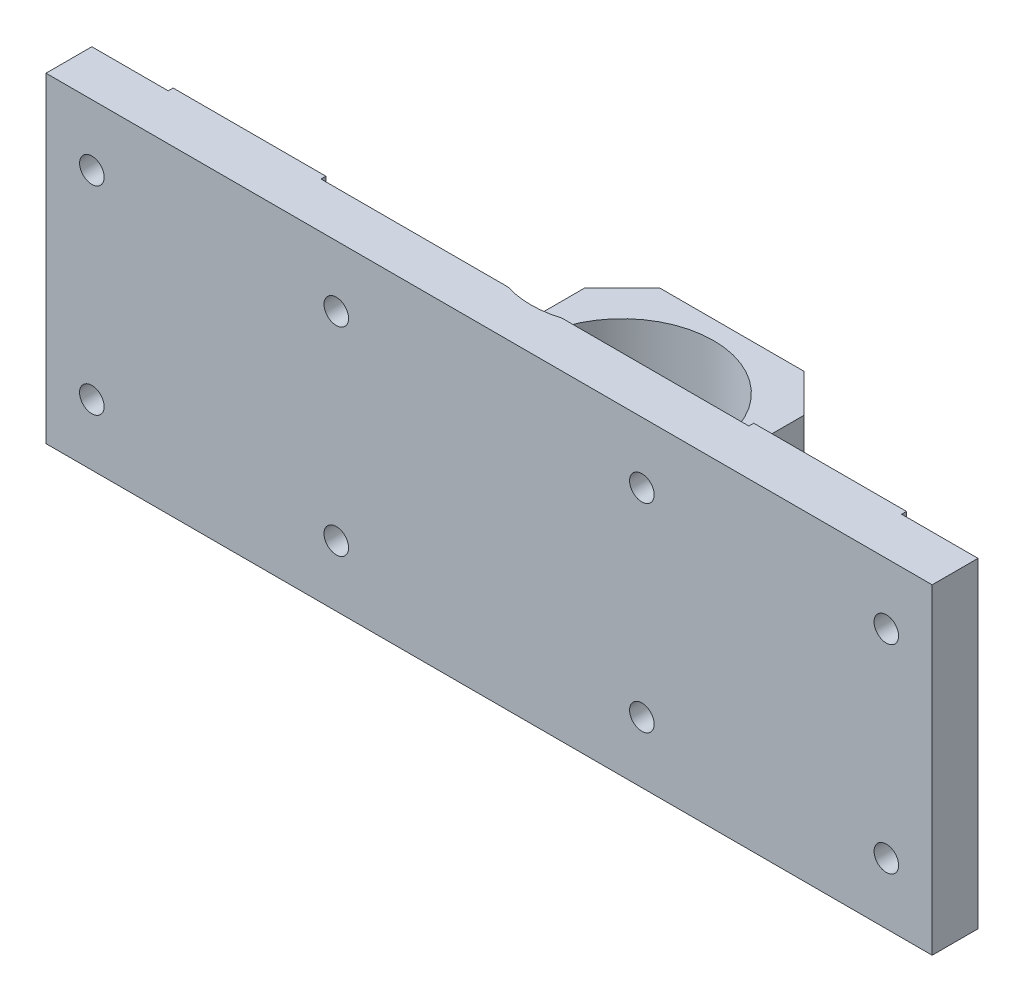
SolidWorks part; units mm, degrees
ref_plane "Front Plane" through (0, 0, 0) normal (0, 0, 1) x (1, 0, 0)
ref_plane "Top Plane" through (0, 0, 0) normal (0, 1, 0) x (1, 0, 0)
ref_plane "Right Plane" through (0, 0, 0) normal (1, 0, 0) x (0, 0, -1)
sketch "Sketch1" plane through (0, 0, 0) normal (0, 0, 1) x (1, 0, 0)
  line L1 (-87.7906, 37.622) -> (96.3594, 37.622)
  line L2 (-87.7906, 37.622) -> (-87.7906, -29.053)
  line L3 (-87.7906, -29.053) -> (96.3594, -29.053)
  line L4 (96.3594, 37.622) -> (96.3594, -29.053)
  dimension "D1" = 184.15
  dimension "D2" = 66.675
extrude "Boss-Extrude1" add sketch "Sketch1" along normal blind 9.525
sketch "Sketch5" plane through (0, 37.622, 0) normal (0, 1, 0) x (1, 0, 0)
  line L0 (10.8884, 0) -> (10.8884, -9.525)
  line L1 (96.3594, 0) -> (-87.7906, 0) construction
  line L2 (96.3594, -9.525) -> (-87.7906, -9.525) construction
  line L3 (-2.3196, 0) -> (-2.3196, -9.525)
  point P8 (4.2844, 0)
  dimension "D1" = 6.604
  dimension "D2" = 6.604
sketch "Sketch6" plane through (0, 37.622, 0) normal (0, 1, 0) x (1, 0, 0)
  arc A0 (10.8884, 0) -> (-2.3196, 0) centre (4.2844, 10.8827) cw
extrude "Cut-Extrude1" cut sketch "Sketch6" against normal through all and the other way through all flip side to cut
sketch "Sketch7" plane through (0, 37.622, 0) normal (0, 1, 0) x (1, 0, 0)
  line L0 (4.2844, -4.7215) -> (4.2844, 18.1385)
  line L1 (-87.7906, -9.525) -> (-87.7906, 0) construction
  circle A1 centre (4.2844, 18.1385) radius 22.8473
  dimension "D1" = 22.86
  dimension "D2" = 92.075
extrude "Boss-Extrude2" add sketch "Sketch7" against normal through all contours A1
sketch "Sketch8" plane through (0, 37.622, 0) normal (0, 1, 0) x (1, 0, 0)
  circle A0 centre (4.2844, 18.1385) radius 18.9865
  dimension "D1" = 37.973
extrude "Cut-Extrude2" cut sketch "Sketch8" against normal blind 61.595
sketch "Sketch9" plane through (0, -23.973, 0) normal (0, 1, 0) x (1, 0, 0)
  circle A0 centre (4.2844, 18.1385) radius 7.9375
  circle A1 centre (4.2844, 18.1385) radius 18.9865 construction
  dimension "D1" = 15.875
  dimension "D2" = 0
extrude "Cut-Extrude3" cut sketch "Sketch9" against normal through all
sketch "Sketch12" plane through (0, 37.622, 0) normal (0, 1, 0) x (1, 0, 0)
  line L0 (27.1317, 18.1385) -> (27.1317, 0)
  line L1 (96.3594, 0) -> (18.1766, 0) construction
  line L2 (27.1317, 0) -> (18.1766, 0)
  line L3 (-18.5629, 18.1385) -> (-18.5629, 0)
  line L4 (-9.6078, 0) -> (-87.7906, 0) construction
  line L5 (-18.5629, 0) -> (-9.6078, 0)
  circle A0 centre (4.2844, 18.1385) radius 22.8473 construction
  arc A1 (18.1766, 0) -> (27.1317, 18.1385) centre (4.2844, 18.1385) ccw
  arc A2 (-9.6078, 0) -> (-18.5629, 18.1385) centre (4.2844, 18.1385) cw
extrude "Boss-Extrude3" add sketch "Sketch12" against normal up to surface (66.675 mm away) up to face at (4.2844, -29.053, -10.201)
sketch "Sketch16" plane through (0, -29.053, 0) normal (0, -1, 0) x (1, 0, 0)
  line L0 (-18.5629, -18.1385) -> (-18.5629, -40.9857)
  line L1 (4.2844, -40.9857) -> (-18.5629, -40.9857)
  arc A0 (-18.5629, -18.1385) -> (27.1317, -18.1385) centre (4.2844, -18.1385) ccw construction
  arc A1 (-18.5629, -18.1385) -> (4.2844, -40.9857) centre (4.2844, -18.1385) ccw
extrude "Boss-Extrude4" add sketch "Sketch16" against normal up to surface (66.675 mm away) up to face at (4.2844, 37.622, -5.0093)
sketch "Sketch18" plane through (0, -29.053, 0) normal (0, -1, 0) x (1, 0, 0)
  line L0 (27.1317, -18.1385) -> (27.1317, -40.9857)
  line L1 (27.1317, -40.9857) -> (4.2844, -40.9857)
  arc A0 (27.1317, -18.1385) -> (4.2844, -40.9857) centre (4.2844, -18.1385) cw
extrude "Boss-Extrude5" add sketch "Sketch18" against normal up to surface (66.675 mm away) up to face at (4.8102, 37.622, -9.5324)
sketch "Sketch19" plane through (0, 37.622, 0) normal (0, 1, 0) x (1, 0, 0)
  line L2 (27.1317, 40.9857) -> (-18.5629, 40.9857) construction
  line L3 (19.2577, 40.9857) -> (27.1317, 40.9857)
  line L6 (-18.5629, 40.9857) -> (-18.5629, 0) construction
  line L8 (-18.5629, 40.9857) -> (-18.5629, 33.1259)
  line L9 (-18.5629, 33.1259) -> (-10.703, 40.9857)
  line L10 (-10.703, 40.9857) -> (-18.5629, 40.9857)
  line L11 (19.2577, 40.9857) -> (27.1317, 33.1117)
  line L12 (27.1317, 0) -> (27.1317, 40.9857) construction
  line L13 (27.1317, 33.1117) -> (27.1317, 40.9857)
  dimension "D1" = 7.8599
  dimension "D2" = 7.874
extrude "Cut-Extrude6" cut sketch "Sketch19" against normal through all
hole_wizard "#10 Clearance Hole1" positions "Sketch23" profile "Sketch24" hole size "#10" standard "ANSI Inch" end condition through all
sketch "Sketch23" plane through (0, 0, 0) normal (0, 0, -1) x (-1, 0, 0)
  line L0 (87.7906, 37.622) -> (87.7906, -29.053) construction
  line L1 (87.7906, -29.053) -> (18.5629, -29.053) construction
  line L2 (18.5629, 37.622) -> (87.7906, 37.622) construction
  line L3 (-96.3594, -29.053) -> (-96.3594, 37.622) construction
  line L4 (-96.3594, 37.622) -> (-27.1317, 37.622) construction
  line L5 (-27.1317, -29.053) -> (-96.3594, -29.053) construction
  point P0 (78.2656, 24.922)
  point P2 (78.2656, -16.353)
  point P4 (-86.8344, -16.353)
  point P6 (-86.8344, 24.922)
  dimension "D1" = 9.525
  dimension "D2" = 12.7
  dimension "D3" = 12.7
  dimension "D4" = 9.525
  dimension "D5" = 9.525
  dimension "D6" = 12.7
  dimension "D7" = 12.7
  dimension "D8" = 9.525
sketch "Sketch24" plane through (-78.2656, 24.922, 0) normal (1, 0, 0) x (0, 1, 0)
  line L0 (0, 0) -> (0, 9.525)
  line L1 (0, 9.525) -> (2.5527, 9.525)
  line L2 (2.5527, 9.525) -> (2.5527, 0)
  line L5 (2.5527, 0) -> (0, 0)
  line L11 (0, -6.35) -> (0, 107.95) construction
  dimension "Thru Hole Dia." = 5.1054
  dimension "Thru Hole Depth" = 9.525
hole_wizard "#10 Clearance Hole2" positions "Sketch25" profile "Sketch26" hole size "#10" standard "ANSI Inch" end condition through all
sketch "Sketch25" plane through (0, 0, 0) normal (0, 0, -1) x (-1, 0, 0)
  line L0 (87.7906, -29.053) -> (18.5629, -29.053) construction
  line L2 (18.5629, 37.622) -> (87.7906, 37.622) construction
  line L3 (-96.3594, 37.622) -> (-27.1317, 37.622) construction
  line L5 (-27.1317, -29.053) -> (-96.3594, -29.053) construction
  circle A0 centre (78.2656, -16.353) radius 2.5527 construction
  circle A1 centre (78.2656, 24.922) radius 2.5527 construction
  circle A2 centre (-86.8344, 24.922) radius 2.5527 construction
  circle A3 centre (-86.8344, -16.353) radius 2.5527 construction
  point P0 (27.4656, -16.353)
  point P2 (27.4656, 24.922)
  point P4 (-36.0344, 24.922)
  point P6 (-36.0344, -16.353)
  dimension "D1" = 12.7
  dimension "D2" = 50.8
  dimension "D3" = 50.8
  dimension "D4" = 12.7
  dimension "D5" = 12.7
  dimension "D6" = 50.8
  dimension "D7" = 50.8
  dimension "D8" = 12.7
sketch "Sketch26" plane through (-27.4656, -16.353, 0) normal (1, 0, 0) x (0, 1, 0)
  line L0 (0, 0) -> (0, 9.525)
  line L1 (0, 9.525) -> (2.5527, 9.525)
  line L2 (2.5527, 9.525) -> (2.5527, 0)
  line L5 (2.5527, 0) -> (0, 0)
  line L11 (0, -6.35) -> (0, 107.95) construction
  dimension "Thru Hole Dia." = 5.1054
  dimension "Thru Hole Depth" = 9.525
sketch "Sketch31" plane through (0, 0, -40.9857) normal (0, 0, -1) x (-1, 0, 0)
  line L1 (-19.2577, -29.053) -> (10.703, -29.053)
  line L2 (-19.2577, -29.053) -> (-19.2577, 37.622)
  line L3 (-19.2577, 37.622) -> (10.703, 37.622)
  line L4 (10.703, -29.053) -> (10.703, 37.622)
extrude "Boss-Extrude6" [suppressed] add sketch "Sketch31" along normal blind 2.54
hole_wizard "3/16 (0.1875) Diameter Hole3" positions "Sketch32" profile "Sketch33" hole size "3/16" standard "ANSI Inch" end condition up to next
sketch "Sketch32" plane through (-25.8444, 0, -25.8444) normal (-0.7071, 0, -0.7071) x (-0.7071, 0, 0.7071)
  line L0 (-10.2976, -29.053) -> (-21.4131, -29.053) construction
  line L1 (-10.2976, -29.053) -> (-10.2976, 37.622) construction
  point P0 (-15.3776, -20.163)
  point P2 (-15.3776, -7.463)
  dimension "D1" = 8.89
  dimension "D2" = 12.7
  dimension "D3" = 5.08
sketch "Sketch33" plane through (-14.9708, -20.163, -36.718) normal (0, 1, 0) x (-0.7071, 0, 0.7071)
  line L0 (0, 0) -> (0, 7.7726)
  line L1 (0, 7.7726) -> (2.3812, 7.7726)
  line L2 (2.3812, 7.7726) -> (2.3812, 0)
  line L5 (2.3812, 0) -> (0, 0)
  line L11 (0, -6.35) -> (0, 107.95) construction
  dimension "Thru Hole Dia." = 4.7625
  dimension "Thru Hole Depth" = 7.7726
hole_wizard "3/16 (0.1875) Diameter Hole4" positions "Sketch34" profile "Sketch35" hole size "3/16" standard "ANSI Inch" end condition up to next
sketch "Sketch34" plane through (30.1217, 0, -30.1217) normal (0.7071, 0, -0.7071) x (-0.7071, 0, -0.7071)
  line L0 (15.3641, -29.053) -> (4.2285, -29.053) construction
  line L1 (4.2285, -29.053) -> (4.2285, 37.622) construction
  point P0 (9.3085, -20.163)
  point P2 (9.3085, -7.463)
  dimension "D1" = 8.89
  dimension "D2" = 12.7
  dimension "D3" = 5.08
sketch "Sketch35" plane through (23.5395, -20.163, -36.7038) normal (0, 1, 0) x (-0.7071, 0, -0.7071)
  line L0 (0, 0) -> (0, 7.7629)
  line L1 (0, 7.7629) -> (2.3812, 7.7629)
  line L2 (2.3812, 7.7629) -> (2.3812, 0)
  line L5 (2.3812, 0) -> (0, 0)
  line L11 (0, -6.35) -> (0, 107.95) construction
  dimension "Thru Hole Dia." = 4.7625
  dimension "Thru Hole Depth" = 7.7629
sketch "Sketch36" plane through (0, 0, 0) normal (0, 0, -1) x (-1, 0, 0)
  line L0 (-96.3594, 37.622) -> (-27.1317, 37.622) construction
  line L1 (-80.4844, 37.622) -> (-48.7344, 37.622)
  line L2 (-80.4844, 37.622) -> (-80.4844, -29.053)
  line L3 (-80.4844, -29.053) -> (-48.7344, -29.053)
  line L4 (-48.7344, 37.622) -> (-48.7344, -29.053)
  line L5 (-27.1317, -29.053) -> (-96.3594, -29.053) construction
  line L6 (18.5629, 37.622) -> (87.7906, 37.622) construction
  line L7 (40.1656, 37.622) -> (71.9156, 37.622)
  line L8 (40.1656, 37.622) -> (40.1656, -29.053)
  line L9 (40.1656, -29.053) -> (71.9156, -29.053)
  line L10 (71.9156, 37.622) -> (71.9156, -29.053)
  line L11 (87.7906, -29.053) -> (18.5629, -29.053) construction
  line L12 (87.7906, 37.622) -> (87.7906, -29.053) construction
  line L13 (-96.3594, -29.053) -> (-96.3594, 37.622) construction
  dimension "D1" = 15.875
  dimension "D2" = 31.75
  dimension "D3" = 15.875
  dimension "D4" = 31.75
extrude "Boss-Extrude7" add sketch "Sketch36" along normal blind 1.016
ref_plane "Plane1" through (4.2844, 0, 0) normal (1, 0, 0) x (0, 0, -1)
sketch "Sketch37" plane through (27.1317, 0, 0) normal (1, 0, 0) x (0, 0, -1)
  line L0 (33.1117, -29.053) -> (0, -29.053) construction
  line L1 (5.4385, -29.053) -> (30.8385, -29.053)
  line L2 (5.4385, -29.053) -> (5.4385, -10.003)
  line L3 (5.4385, -10.003) -> (30.8385, -10.003)
  line L4 (30.8385, -29.053) -> (30.8385, -10.003)
  line L5 (18.1385, -23.973) -> (18.1385, 37.622) construction
  line L6 (18.1385, 37.622) -> (18.1385, -32.4273) construction
  line L7 (40.9857, 37.622) -> (-4.7088, 37.622) construction
  dimension "D1" = 25.4
  dimension "D2" = 19.05
sketch "Sketch43" plane through (0, 37.622, 0) normal (0, 1, 0) x (1, 0, 0)
  line L0 (27.1317, 0) -> (-18.5629, 0)
  line L1 (27.1317, 0) -> (27.1317, 42.6742)
  line L2 (-18.5629, 0) -> (-18.5629, 42.6742)
  line L3 (27.1317, 42.6742) -> (-18.5629, 42.6742)
extrude "Cut-Extrude8" cut sketch "Sketch43" against normal blind 25.4
